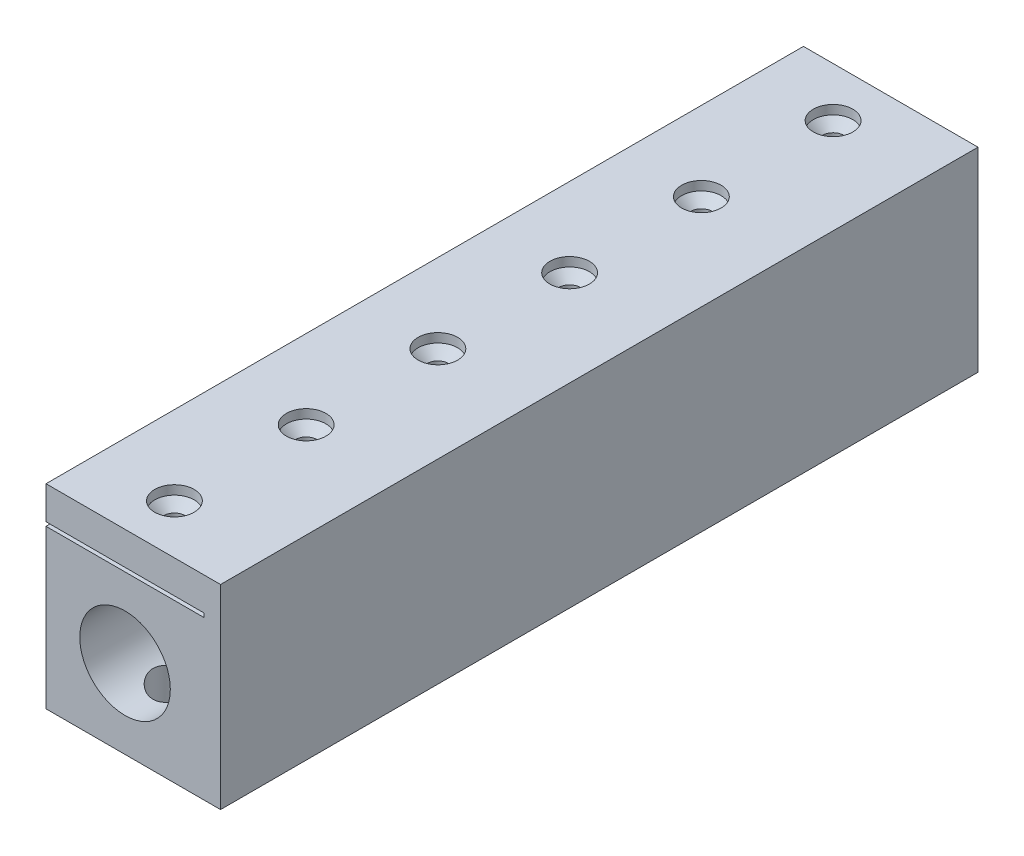
SolidWorks part; units mm, degrees
ref_plane "Front Plane" through (0, 0, 0) normal (0, 0, 1) x (1, 0, 0)
ref_plane "Top Plane" through (0, 0, 0) normal (0, 1, 0) x (1, 0, 0)
ref_plane "Right Plane" through (0, 0, 0) normal (1, 0, 0) x (0, 0, -1)
sketch "Sketch1" plane through (0, 0, 0) normal (0, 0, 1) x (1, 0, 0)
  line L1 (-24, -24) -> (24, -24)
  line L2 (-24, -24) -> (-24, 24)
  line L3 (-24, 24) -> (24, 24)
  line L4 (24, -24) -> (24, 24)
  line L5 (-24, -24) -> (24, 24) construction
  line L6 (-24, 24) -> (24, -24) construction
  line L7 (24, -24) -> (29, -24)
  line L8 (24, -24) -> (24, 35.2)
  line L9 (24, 35.2) -> (29, 35.2)
  line L10 (29, -24) -> (29, 35.2)
  line L11 (24, 35.2) -> (-24, 35.2)
  line L12 (24, 35.2) -> (24, 25.2)
  line L13 (24, 25.2) -> (-24, 25.2)
  line L14 (-24, 35.2) -> (-24, 25.2)
  circle A0 centre (0, 0) radius 13.75
  dimension "D1" = 27.5
  dimension "D2" = 1.2
  dimension "D3" = 48
  dimension "D4" = 48
  dimension "D5" = 5
  dimension "D6" = 10
extrude "Boss-Extrude1" add sketch "Sketch1" along normal blind 230 contours L1 L4 L3 L2 A0 | L11 L14 L13 L8 | L7 L10 L9 L8 L4 region at (-23.3212, 0, 0) region at (26.5, 5.6, 0) region at (0, 30.2, 0)
sketch "Sketch3" plane through (0, 35.2, 0) normal (0, 1, 0) x (1, 0, 0)
  line L0 (0, 0) -> (0, -230) construction
  line L1 (-24, -230) -> (29, -230) construction
  circle A0 centre (0, -15) radius 6
  circle A1 centre (0, -55) radius 6
  circle A2 centre (0, -95) radius 6
  circle A3 centre (0, -135) radius 6
  circle A4 centre (0, -175) radius 6
  circle A5 centre (0, -215) radius 6
  dimension "D1" = 12
  dimension "D2" = 15
  dimension "D4" = 15
  dimension "D3" = 6
extrude "Cut-Extrude1" cut sketch "Sketch3" against normal blind 0.5
sketch "Sketch4" plane through (0, 35.2, 0) normal (0, 1, 0) x (1, 0, 0)
  line L0 (0, 0) -> (0, -230) construction
  line L1 (-24, -230) -> (29, -230) construction
  circle A0 centre (0, -15) radius 3.25
  circle A1 centre (0, -55) radius 3.25
  circle A2 centre (0, -95) radius 3.25
  circle A3 centre (0, -135) radius 3.25
  circle A4 centre (0, -175) radius 3.25
  circle A5 centre (0, -215) radius 3.25
  dimension "D1" = 6.5
  dimension "D2" = 6
extrude "Cut-Extrude2" cut sketch "Sketch4" against normal through all
sketch "Sketch5" plane through (0, -24, 0) normal (0, -1, 0) x (1, 0, 0)
  line L0 (0, 230) -> (0, 0) construction
  line L1 (-24, 230) -> (29, 230) construction
  circle A0 centre (0, 215) radius 6.5
  circle A1 centre (0, 175) radius 6.5
  circle A2 centre (0, 135) radius 6.5
  circle A3 centre (0, 95) radius 6.5
  circle A4 centre (0, 55) radius 6.5
  circle A5 centre (0, 15) radius 6.5
  dimension "D1" = 13
  dimension "D2" = 6
extrude "Cut-Extrude3" cut sketch "Sketch5" against normal up to next
sketch "Sketch7" plane through (0, 24, 0) normal (0, 1, 0) x (1, 0, 0)
  line L0 (0, 0) -> (0, -230) construction
  line L1 (0, -8.5337) -> (-5.6, -11.7668)
  line L2 (-5.6, -11.7668) -> (-5.6, -18.2332)
  line L3 (-5.6, -18.2332) -> (0, -21.4663)
  line L4 (0, -21.4663) -> (5.6, -18.2332)
  line L5 (5.6, -18.2332) -> (5.6, -11.7668)
  line L6 (5.6, -11.7668) -> (0, -8.5337)
  line L7 (-24, -230) -> (29, -230) construction
  line L8 (0, -48.5337) -> (-5.6, -51.7668)
  line L9 (-5.6, -51.7668) -> (-5.6, -58.2332)
  line L10 (-5.6, -58.2332) -> (0, -61.4663)
  line L11 (0, -61.4663) -> (5.6, -58.2332)
  line L12 (5.6, -58.2332) -> (5.6, -51.7668)
  line L13 (5.6, -51.7668) -> (0, -48.5337)
  line L14 (0, -88.5337) -> (-5.6, -91.7668)
  line L15 (-5.6, -91.7668) -> (-5.6, -98.2332)
  line L16 (-5.6, -98.2332) -> (0, -101.4663)
  line L17 (0, -101.4663) -> (5.6, -98.2332)
  line L18 (5.6, -98.2332) -> (5.6, -91.7668)
  line L19 (5.6, -91.7668) -> (0, -88.5337)
  line L20 (0, -128.5337) -> (-5.6, -131.7668)
  line L21 (-5.6, -131.7668) -> (-5.6, -138.2332)
  line L22 (-5.6, -138.2332) -> (0, -141.4663)
  line L23 (0, -141.4663) -> (5.6, -138.2332)
  line L24 (5.6, -138.2332) -> (5.6, -131.7668)
  line L25 (5.6, -131.7668) -> (0, -128.5337)
  line L26 (0, -168.5337) -> (-5.6, -171.7668)
  line L27 (-5.6, -171.7668) -> (-5.6, -178.2332)
  line L28 (-5.6, -178.2332) -> (0, -181.4663)
  line L29 (0, -181.4663) -> (5.6, -178.2332)
  line L30 (5.6, -178.2332) -> (5.6, -171.7668)
  line L31 (5.6, -171.7668) -> (0, -168.5337)
  line L32 (0, -208.5337) -> (-5.6, -211.7668)
  line L33 (-5.6, -211.7668) -> (-5.6, -218.2332)
  line L34 (-5.6, -218.2332) -> (0, -221.4663)
  line L35 (0, -221.4663) -> (5.6, -218.2332)
  line L36 (5.6, -218.2332) -> (5.6, -211.7668)
  line L37 (5.6, -211.7668) -> (0, -208.5337)
  circle A0 centre (0, -15) radius 5.6 construction
  dimension "D1" = 11.2
  dimension "D2" = 6
extrude "Cut-Extrude4" cut sketch "Sketch7" against normal up to next from offset 5 offset against normal yes
chamfer "Chamfer1" distance 5 angle 45 6 edges at (0, 34.7, 218.25) (0, 34.7, 178.25) (0, 34.7, 138.25) (0, 34.7, 98.25) (0, 34.7, 58.25) (0, 34.7, 18.25)
